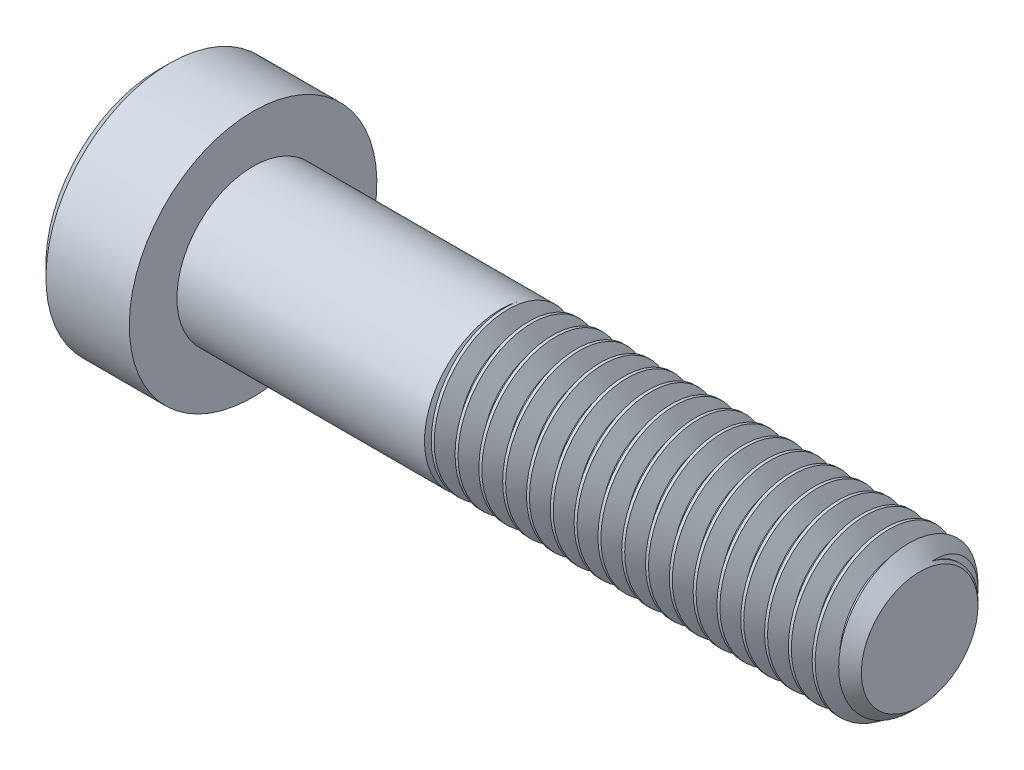
SolidWorks part; units mm, degrees
ref_plane "Front Plane" through (0, 0, 0) normal (0, 0, 1) x (1, 0, 0)
ref_plane "Top Plane" through (0, 0, 0) normal (0, 1, 0) x (1, 0, 0)
ref_plane "Right Plane" through (0, 0, 0) normal (1, 0, 0) x (0, 0, -1)
sketch "Sketch1" plane through (0, 0, 0) normal (0, 0, 1) x (1, 0, 0)
  line L0 (17.5, 0) -> (-17.5, 0) construction
  line L1 (17.5, 4) -> (17.5, -4) construction
  line L2 (-17.5, 6.5) -> (-17.5, -6.5) construction
  line L3 (-17.5, 6.5) -> (-21.875, 6.5) construction
  line L4 (-21.875, 6.5) -> (-22.5, 5.875) construction
  line L5 (-22.5, 5.875) -> (-22.5, -5.875) construction
  line L6 (-22.5, -5.875) -> (-21.875, -6.5) construction
  line L7 (-21.875, -6.5) -> (-17.5, -6.5) construction
  line L8 (-4.5, 4) -> (-4.5, -4) construction
  point P7 (-18.55, 0)
  point P12 (12.5, -4)
  dimension "D1" = 45
  dimension "D2" = 5
  dimension "Dec." = 8
  dimension "Length" = 35
  dimension "Head Dia" = 13
  dimension "Head Height" = 5
  dimension "Hex Depth" = 3.95
  dimension "Chamfer" = 0.625
  dimension "Thread Length" = 22
ref_plane "Plane1" through (17.5, 0, 0) normal (1, 0, 0) x (0, 0, -1)
ref_plane "Plane2" through (-22.5, 0, 0) normal (1, 0, 0) x (0, 0, -1)
sketch "Sketch2" plane through (17.5, 0, 0) normal (1, 0, 0) x (0, 0, -1)
  circle A0 centre (0, 0) radius 4
extrude "Boss-Extrude1" add sketch "Sketch2" against normal up to vertex (22 mm away) up to point (-4.5, 4, 0)
sketch "Sketch3" plane through (17.5, 0, 0) normal (1, 0, 0) x (0, 0, -1)
  circle A0 centre (0, 0) radius 4 construction
  circle A1 centre (0, 0) radius 4
curve "Helix/Spiral1" pitch 1.25 height 23.25 radius 4 centre (17.5, 0, 0) axis (-1, 0, 0) start towards (0, 1, 0) parameters "Pitch"=1.25
chamfer "Chamfer1" distance 0.9375 angle 45 1 edges at (17.5, 0, -4)
sketch "Sketch5" plane through (0, 0, 0) normal (0, 0, 1) x (1, 0, 0)
  line L0 (16.9531, 4) -> (18.0469, 4)
  line L1 (18.0469, 4) -> (17.5781, 3.1881)
  line L2 (17.5781, 3.1881) -> (17.4219, 3.1881)
  line L3 (17.4219, 3.1881) -> (16.9531, 4)
  line L4 (17.5, 3.1881) -> (17.5, 4) construction
  line L5 (17.1875, 3.5941) -> (17.8125, 3.5941) construction
  dimension "D1" = 60
  dimension "D2" = 0.625
  dimension "D3" = 0.1562
sweep "Cut-Sweep1" cut profiles "Sketch5" path "Helix/Spiral1" align with end faces yes
sketch "Sketch4" plane through (-22.5, 0, 0) normal (1, 0, 0) x (0, 0, -1)
  line L0 (-6.5, 0.7937) -> (6.5, 0.7937) construction
  line L1 (0, 2.8868) -> (-2.5, 1.4434)
  line L2 (-2.5, 1.4434) -> (-2.5, -1.4434)
  line L3 (-2.5, -1.4434) -> (0, -2.8868)
  line L4 (0, -2.8868) -> (2.5, -1.4434)
  line L5 (2.5, -1.4434) -> (2.5, 1.4434)
  line L6 (2.5, 1.4434) -> (0, 2.8868)
  line L7 (0, 0) -> (0, 0.7937) construction
  circle A0 centre (0, 0) radius 2.5 construction
  dimension "D1" = 13
  dimension "Hex Size" = 5
  dimension "D2" = 0.7937
sketch "Sketch10" plane through (0, 0, 0) normal (0, 0, 1) x (1, 0, 0)
  line L0 (-17.5, 0) -> (-2.1906, 0) construction
  line L1 (-2.1906, 0) -> (-4.5, 4)
  line L2 (-4.5, 4) -> (-17.5, 4)
  line L3 (-17.5, 4) -> (-17.5, 0)
  line L4 (-17.5, 6.5) -> (-17.5, -6.5) construction
  line L5 (-17.5, 0) -> (-2.1906, 0)
  dimension "D1" = 60
revolve "Revolve2" add sketch "Sketch10" angle 360 about L0
sketch "Sketch6" plane through (0, 0, 0) normal (0, 0, 1) x (1, 0, 0)
  line L0 (-21.875, 6.5) -> (-22.5, 5.875) construction
  line L1 (-17.5, 6.5) -> (-21.875, 6.5) construction
  line L2 (-17.5, 6.5) -> (-17.5, -6.5) construction
  line L3 (-22.5, 5.875) -> (-22.5, -5.875) construction
  line L4 (-21.875, 6.5) -> (-22.5, 5.875)
  line L5 (-17.5, 6.5) -> (-21.875, 6.5)
  line L6 (-17.5, 6.5) -> (-17.5, 0)
  line L7 (-22.5, 5.875) -> (-22.5, 0)
  line L8 (-17.5, 0) -> (-22.5, 0) construction
  line L9 (-17.5, 0) -> (-22.5, 0)
revolve "Revolve1" add sketch "Sketch6" angle 360 about L8
extrude "Cut-Extrude1" cut sketch "Sketch4" along normal up to vertex (3.95 mm away) up to point (-18.55, 0, 0)
sketch "Sketch8" plane through (-22.5, 0, 0) normal (-1, 0, 0) x (0, 0, 1)
  circle A1 centre (0, 0) radius 2.8868
extrude "Cut-Extrude2" cut sketch "Sketch8" against normal through all draft 45
equation "\"D3@Helix/Spiral1\" = \"Thread Length@Sketch1\"+\"Pitch@Helix/Spiral1\""
equation "\"D3@Sketch5\" = \"Pitch@Helix/Spiral1\"*.125"
equation "\"D2@Sketch5\" = \"Pitch@Helix/Spiral1\"*.50"
equation "\"D1@Chamfer1\" = \"Pitch@Helix/Spiral1\"*.75"
equation "\"D2@Sketch1\" = \"Pitch@Helix/Spiral1\"*4"
equation "\"D1@Sketch4\" = \"Head Dia@Sketch1\""
equation "\"Chamfer@Sketch1\" = \"Head Height@Sketch1\"/8"
